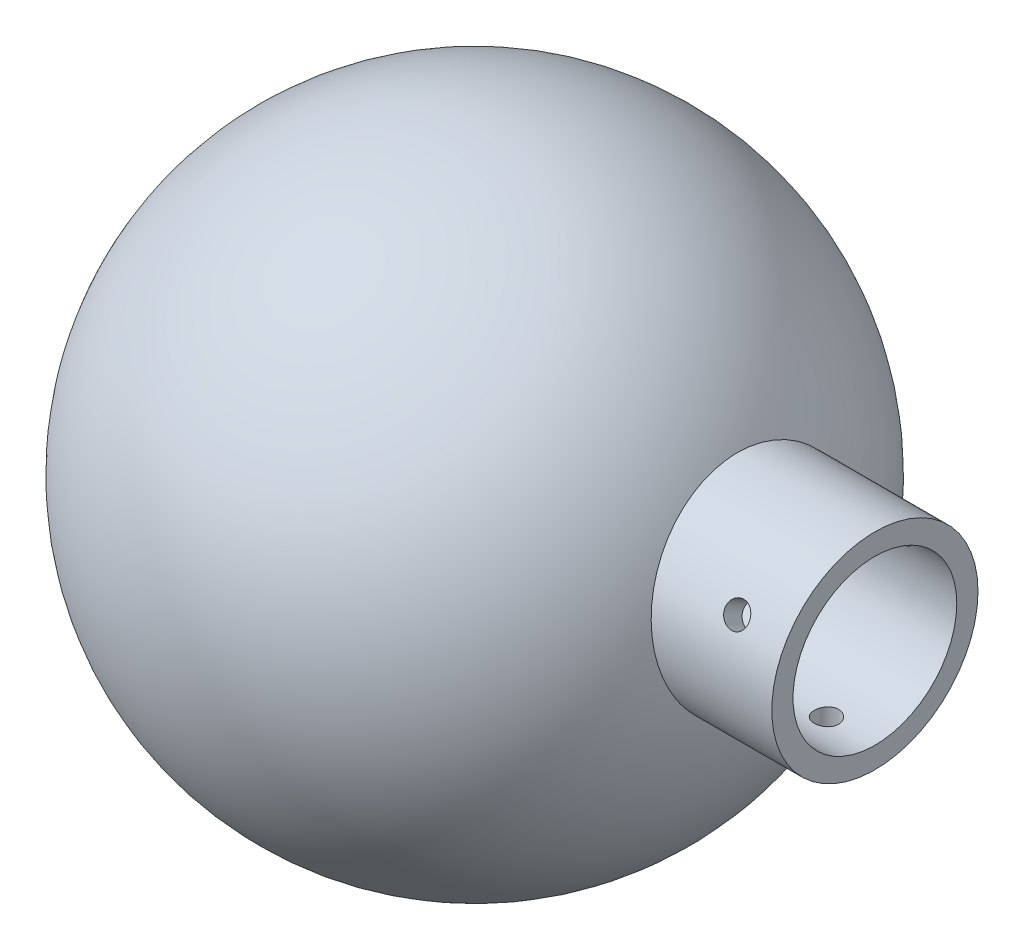
SolidWorks part; units mm, degrees
ref_plane "Front Plane" through (0, 0, 0) normal (0, 0, 1) x (1, 0, 0)
ref_plane "Top Plane" through (0, 0, 0) normal (0, 1, 0) x (1, 0, 0)
ref_plane "Right Plane" through (0, 0, 0) normal (1, 0, 0) x (0, 0, -1)
sketch "Sketch1" plane through (0, 0, 0) normal (0, 0, 1) x (1, 0, 0)
  line L0 (-63.5, 0) -> (-60.96, 0)
  line L1 (60.96, 0) -> (63.5, 0)
  arc A0 (63.5, 0) -> (-63.5, 0) centre (0, 0) ccw
  arc A1 (60.96, 0) -> (-60.96, 0) centre (0, 0) ccw
  dimension "D1" = 63.5
  dimension "D2" = 60.96
revolve "Revolve1" add sketch "Sketch1" angle 360 about L0
sketch "Sketch2" plane through (0, 0, 0) normal (1, 0, 0) x (0, 0, -1)
  line L0 (0, 69.85) -> (0, -69.85) construction
  line L1 (69.85, 0) -> (-69.85, 0) construction
  circle A0 centre (0, 10.0076) radius 21.59
  circle A1 centre (0, 10.0076) radius 17.145
  dimension "D1" = 10.0076
  dimension "D2" = 34.29
  dimension "D3" = 43.18
extrude "Boss-Extrude1" add sketch "Sketch2" along normal blind 83.82 and the other way up to next
extrude "Cut-Extrude3" cut sketch "Sketch2<4>" along normal blind 138.938 contours A1
sketch "Sketch2<4>" plane through (0, 0, 0) normal (1, 0, 0) x (0, 0, -1) same geometry as "Sketch2"
sketch "Sketch4" plane through (0, 0, 0) normal (0, 1, 0) x (1, 0, 0)
  line L0 (-55, 0) -> (55, 0) construction
  line L1 (83.82, -21.59) -> (83.82, 21.59) construction
  circle A0 centre (73.66, 0) radius 2.54
  dimension "D1" = 10.16
extrude "Cut-Extrude4" cut sketch "Sketch4" against normal blind 138.938
pattern_circular "CirPattern1" count 3 every 120 about axis through (-63.502, 10.0076, 0) along (1, 0, 0) of "Cut-Extrude4"
